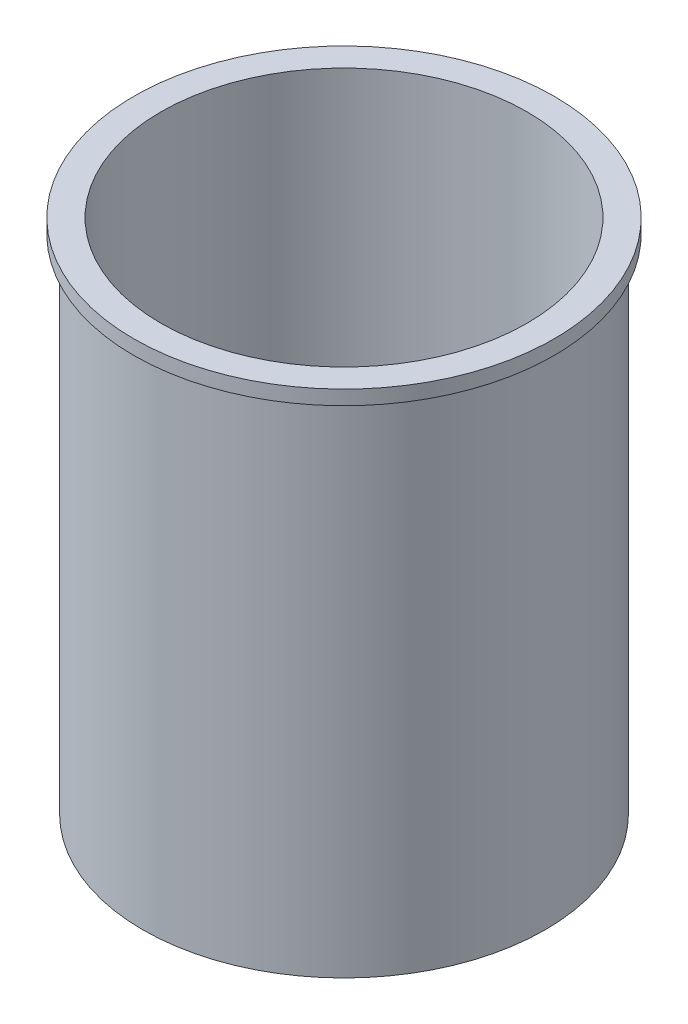
SolidWorks part; units mm, degrees
material "Ceramic Porcelain"
ref_plane "Front Plane" through (0, 0, 0) normal (0, 0, 1) x (1, 0, 0)
ref_plane "Top Plane" through (0, 0, 0) normal (0, 1, 0) x (1, 0, 0)
ref_plane "Right Plane" through (0, 0, 0) normal (1, 0, 0) x (0, 0, -1)
sketch "Pot Base Sketch" plane through (0, 0, 0) normal (0, 1, 0) x (1, 0, 0)
  circle A0 centre (0, 0) radius 167.5
  dimension "D1" = 335
extrude "Pot Base" add sketch "Pot Base Sketch" along normal blind 15
sketch "Pot Wall Sketch" plane through (0, 0, 0) normal (0, 1, 0) x (1, 0, 0)
  circle A0 centre (0, 0) radius 167.5
  circle A1 centre (0, 0) radius 152.5
  dimension "D1" = 335
  dimension "D2" = 305
extrude "Pot Wall" add sketch "Pot Wall Sketch" along normal blind 430
sketch "Pot Rim Sketch" plane through (0, 0, 0) normal (0, 1, 0) x (1, 0, 0)
  circle A0 centre (0, 0) radius 175
  circle A1 centre (0, 0) radius 152.5
  dimension "D1" = 350
  dimension "D2" = 305
extrude "Pot Rim" add sketch "Pot Rim Sketch" along normal blind 12 from offset 418
